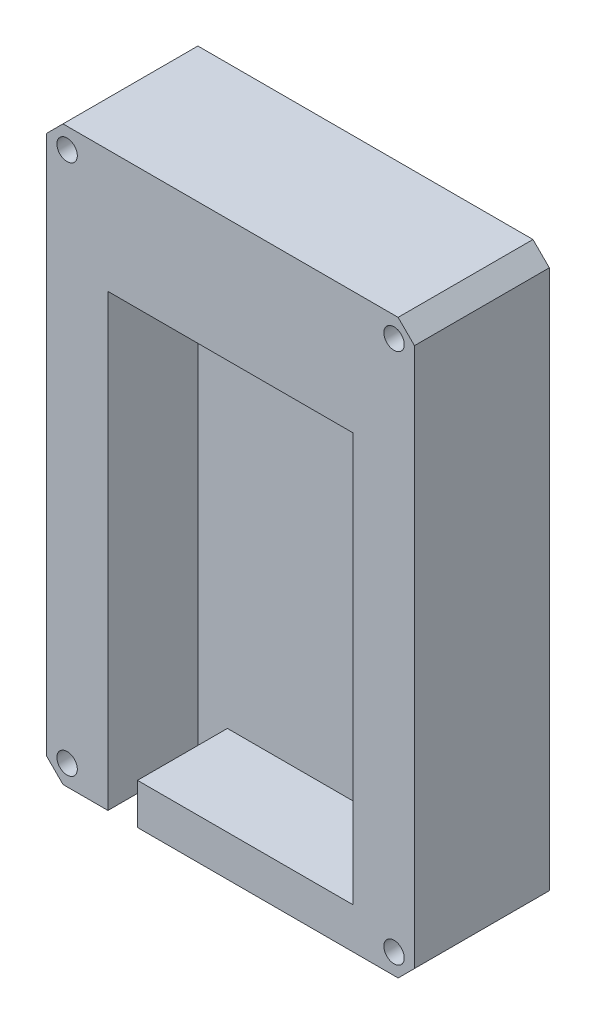
SolidWorks part; units mm, degrees
ref_plane "Front Plane" through (0, 0, 0) normal (0, 0, 1) x (1, 0, 0)
ref_plane "Top Plane" through (0, 0, 0) normal (0, 1, 0) x (1, 0, 0)
ref_plane "Right Plane" through (0, 0, 0) normal (1, 0, 0) x (0, 0, -1)
sketch "Sketch1" plane through (0, 0, 0) normal (0, 0, 1) x (1, 0, 0)
  line L0 (22.5, -35) -> (22.5, 35)
  line L1 (-15, -30) -> (15, -30)
  line L2 (-15, -30) -> (-15, 20)
  line L3 (-15, 20) -> (15, 20)
  line L4 (15, -30) -> (15, 20)
  line L5 (-15, -30) -> (15, 20) construction
  line L6 (-15, 20) -> (15, -30) construction
  line L7 (-22.5, 35) -> (22.5, 35)
  line L8 (-22.5, -35) -> (-22.5, 35)
  line L9 (-22.5, -35) -> (22.5, -35)
  line L10 (0, -35) -> (0, -30) construction
  line L11 (0, 20) -> (0, 0) construction
  line L12 (-15, -30) -> (-15, -35)
  line L13 (-20, -32.5) -> (-20, 32.5) construction
  line L14 (-20, 32.5) -> (20, 32.5) construction
  line L15 (20, -32.5) -> (20, 32.5) construction
  line L16 (-20, -32.5) -> (20, -32.5) construction
  line L17 (-11.3885, -30) -> (-11.3885, -35)
  dimension "D1" = 65
  dimension "D2" = 40
  dimension "D4" = 70
  dimension "D3" = 30
  dimension "D5" = 45
  dimension "D6" = 2.5
  dimension "D7" = 2.5
  dimension "D8" = 5
  dimension "D9" = 50
  dimension "D10" = 35
  dimension "D11" = 22.5
  dimension "D12" = 3.6115
extrude "Boss-Extrude1" add sketch "Sketch1" along normal blind 11 contours L1 L9 L0 L7 L8 L2 L3 L4 region at (5.5558, -34.1678, 0)
extrude "Boss-Extrude2" add sketch "Sketch1<3>" against normal blind 5.5 contours L1 L9 L0 L7 L8 L2 L3 L4 | L1 L4 L3 L2 | L1 L9 region at (5.5558, -34.1678, 0) region at (-13.1942, -32.5, 0) region at (0, -5, 0)
sketch "Sketch1<3>" plane through (0, 0, 0) normal (0, 0, 1) x (1, 0, 0) same geometry as "Sketch1"
sketch "Sketch2" plane through (0, 0, -5.5) normal (0, 0, -1) x (-1, 0, 0)
  point P0 (20, 32.5)
  point P3 (-20, 32.5)
  point P6 (-20, -32.5)
  point P9 (20, -32.5)
hole_wizard "Tap Drill for M3 Tap1" positions "Sketch2" profile "Sketch3" hole size "M3" standard "ISO" end condition through all
sketch "Sketch3" plane through (-20, 32.5, -5.5) normal (1, 0, 0) x (0, 1, 0)
  line L0 (0, 0) -> (0, 16.5)
  line L1 (0, 16.5) -> (1.25, 16.5)
  line L2 (1.25, 16.5) -> (1.25, 0.025)
  line L3 (1.25, 0.025) -> (1.275, 0)
  line L5 (1.275, 0) -> (0, 0)
  line L6 (-1.25, 0.025) -> (-1.275, 0) construction
  line L11 (0, -6.35) -> (0, 107.95) construction
  dimension "Thru Hole Dia." = 2.5
  dimension "Thru Hole Depth" = 16.5
  dimension "Near C'Sink Dia." = 2.55
  dimension "Near C'Sink Angle" = 90
chamfer "Chamfer1" distance 2 angle 45 4 edges at (22.5, -35, 2.75) (22.5, 35, 2.75) (-22.5, 35, 2.75) (-22.5, -35, 2.75)
